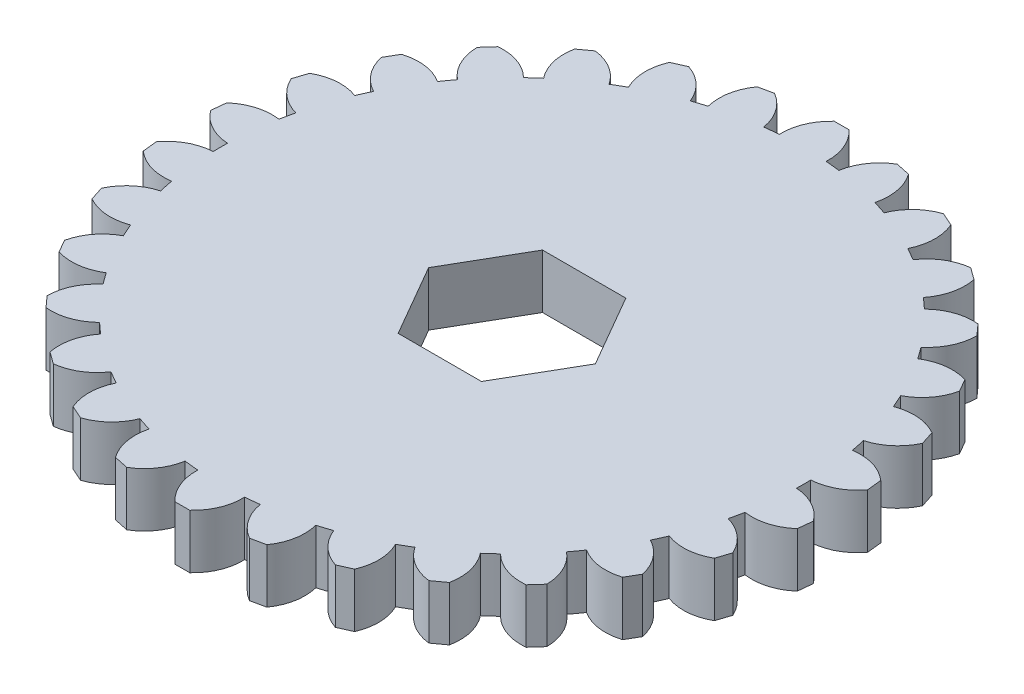
SolidWorks part; units mm, degrees
ref_plane "Front Plane" through (0, 0, 0) normal (0, 0, 1) x (1, 0, 0)
ref_plane "Top Plane" through (0, 0, 0) normal (0, 1, 0) x (1, 0, 0)
ref_plane "Right Plane" through (0, 0, 0) normal (1, 0, 0) x (0, 0, -1)
sketch "Sketch2" plane through (0, 0, 0) normal (0, 1, 0) x (1, 0, 0)
  line L1 (7.3323, 0) -> (3.6662, 6.35)
  line L2 (3.6662, 6.35) -> (-3.6662, 6.35)
  line L3 (-3.6662, 6.35) -> (-7.3323, 0)
  line L4 (-7.3323, 0) -> (-3.6662, -6.35)
  line L5 (-3.6662, -6.35) -> (3.6662, -6.35)
  line L6 (3.6662, -6.35) -> (7.3323, 0)
  circle A0 centre (0, 0) radius 25.6642
  circle A1 centre (0, 0) radius 6.35 construction
  dimension "D1" = 51.3283
  dimension "D2" = 12.7
  dimension "D3" = 6.35
extrude "Boss-Extrude2" add sketch "Sketch2" along normal blind 4.7625
sketch "Sketch1" plane through (0, 0, 0) normal (0, 1, 0) x (1, 0, 0)
  line L0 (0, 0) -> (-3.0476, 28.996) construction
  line L1 (0, 0) -> (3.0476, 28.996) construction
  line L2 (3.0476, 28.996) -> (-3.0476, 28.996) construction
  line L3 (-0.6454, 28.996) -> (0.6454, 28.996)
  line L4 (1.731, 27.4455) -> (2.0597, 25.5814) construction
  line L5 (-1.731, 27.4455) -> (-2.0597, 25.5814) construction
  line L6 (-1.731, 27.4455) -> (-0.6454, 28.996) construction
  line L7 (1.731, 27.4455) -> (0.6454, 28.996) construction
  line L8 (0, 28.996) -> (0, 0) construction
  arc A1 (-2.7554, 25.5158) -> (2.0597, 25.5814) centre (0, 0) cw
  arc A2 (-0.6454, 28.996) -> (-2.0597, 25.5814) centre (2.3088, 25.7721) ccw
  arc A3 (0.6454, 28.996) -> (2.0597, 25.5814) centre (-2.3088, 25.7721) cw
  circle A4 centre (0, 0) radius 25.6642 construction
  circle A5 centre (0, 0) radius 27.5 construction
  point P6 (0, 25.6642)
  point P11 (2.107, 25.5814)
  point P15 (0, 0)
  point P16 (0, 0)
  point P18 (-1.731, 27.4455)
  point P19 (0, 0)
  point P20 (0, 0)
  point P21 (0, 0)
  point P24 (0, 0)
  point P25 (0, 0)
  point P26 (0, 0)
  point P28 (0, 0)
  point P29 (0, 0)
  point P30 (0, 0)
  point P31 (0, 0)
  point P32 (0, 0)
  dimension "D1" = 55
  dimension "D8" = 3.4924
  dimension "D9" = 51.3283
  dimension "D2" = 12
  dimension "D6" = 10
  dimension "D7" = 35
  dimension "D3" = 4.8226
  dimension "D4" = 2.55
  dimension "D5" = 1.56
extrude "Boss-Extrude3" add sketch "Sketch1" along normal blind 4.7625 contours L3 A2 A1 region at (0, 0, -27.086)
pattern_circular "CirPattern1" count 30 over 360 about axis through (0, 4.7625, 0) along (0, -1, 0) of "Boss-Extrude3"
